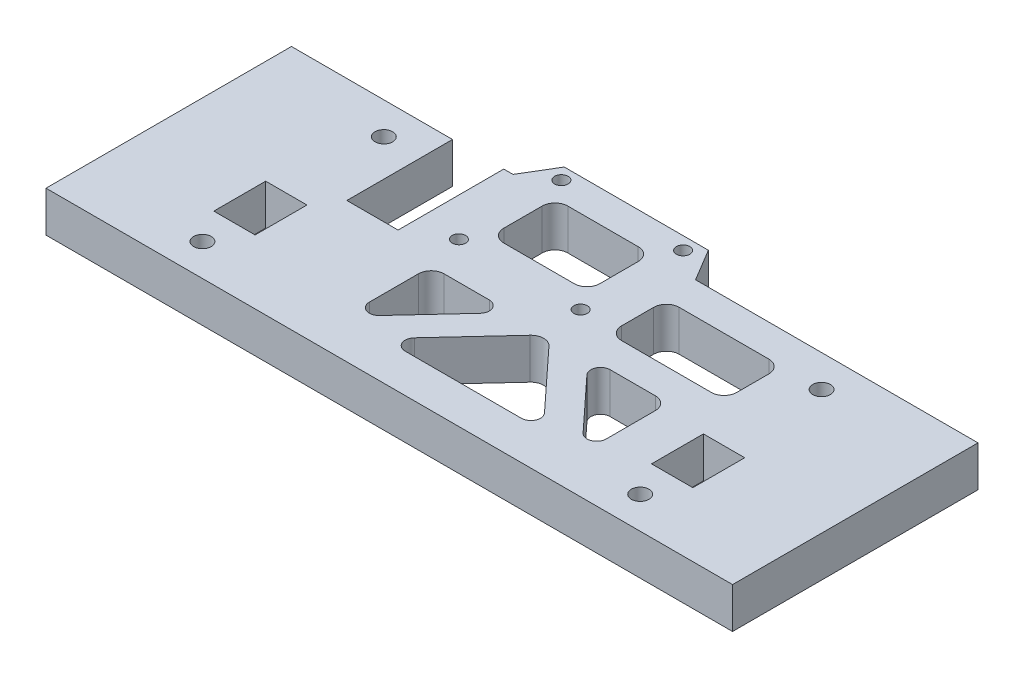
SolidWorks part; units mm, degrees
material "6061 Alloy"
ref_plane "Front Plane" through (0, 0, 0) normal (0, 0, 1) x (1, 0, 0)
ref_plane "Top Plane" through (0, 0, 0) normal (0, 1, 0) x (1, 0, 0)
ref_plane "Right Plane" through (0, 0, 0) normal (1, 0, 0) x (0, 0, -1)
sketch "Sketch1" plane through (0, 0, 0) normal (0, 1, 0) x (1, 0, 0)
  line L0 (107.2, 76.65) -> (107.2, 0) construction
  line L1 (0, 0) -> (214.4, 0)
  line L2 (0, 0) -> (0, 76.65)
  line L4 (214.4, 0) -> (214.4, 76.65)
  line L5 (32.4, 36.2) -> (45.3, 36.2)
  line L6 (32.4, 36.2) -> (32.4, 20)
  line L7 (32.4, 20) -> (45.3, 20)
  line L8 (45.3, 36.2) -> (45.3, 20)
  line L9 (182, 20) -> (169.1, 20)
  line L10 (169.1, 36.2) -> (169.1, 20)
  line L11 (182, 36.2) -> (169.1, 36.2)
  line L12 (182, 36.2) -> (182, 20)
  line L13 (0, 76.65) -> (69.2, 76.65)
  line L14 (69.2, 76.65) -> (75.2, 86.65)
  line L15 (75.2, 86.65) -> (120.2, 86.65)
  line L16 (120.2, 86.65) -> (126.2, 76.65)
  line L17 (126.2, 76.65) -> (214.4, 76.65)
  line L18 (32.4, 28.1) -> (45.3, 28.1) construction
  circle A0 centre (38.85, 66.65) radius 2.75
  circle A5 centre (38.85, 10) radius 2.75
  circle A6 centre (175.55, 66.65) radius 2.75
  circle A7 centre (175.55, 10) radius 2.75
  dimension "D12" = 5.5
  dimension "D16" = 5.5
  dimension "D1" = 214.4
  dimension "D2" = 76.65
  dimension "D3" = 20
  dimension "D5" = 61.9
  dimension "D6" = 12.9
  dimension "D4" = 10
  dimension "D7" = 6
  dimension "D8" = 38
  dimension "D9" = 76.65
  dimension "D10" = 45
  dimension "D11" = 16.2
  dimension "D14" = 6
  dimension "D13" = 10
  dimension "D15" = 10
extrude "Boss-Extrude1" add sketch "Sketch1" along normal blind 12.7
sketch "Sketch2" plane through (0, 12.7, 0) normal (0, 1, 0) x (1, 0, 0)
  line L1 (50.3, 85.2461) -> (66.3, 85.2461)
  line L2 (50.3, 85.2461) -> (50.3, 43.65)
  line L3 (50.3, 43.65) -> (66.3, 43.65)
  line L4 (66.3, 85.2461) -> (66.3, 43.65)
  line L5 (45.3, 20) -> (45.3, 36.2) construction
  line L12 (69.2, 76.65) -> (0, 76.65) construction
  dimension "D1" = 5
  dimension "D2" = 16
  dimension "D3" = 33
extrude "Cut-Extrude1" cut sketch "Sketch2" against normal through all
sketch "Sketch3" plane through (0, 12.7, 0) normal (0, 1, 0) x (1, 0, 0)
  line L1 (66.3, 43.65) -> (66.3, 76.65) construction
  line L2 (120.2, 86.65) -> (75.2, 86.65) construction
  circle A0 centre (78.3, 82.65) radius 2.1
  circle A1 centre (78.3, 50.65) radius 2.1
  circle A2 centre (116.3, 82.65) radius 2.1
  circle A3 centre (116.3, 50.65) radius 2.1
  point P9 (0, 0)
  dimension "D2" = 4.2
  dimension "D5" = 4.2
  dimension "D8" = 32
  dimension "D1" = 4
  dimension "D3" = 12
  dimension "D4" = 32
  dimension "D7" = 38
  dimension "D6" = 2
extrude "Cut-Extrude2" cut sketch "Sketch3" against normal through all
sketch "Sketch5" plane through (0, 12.7, 0) normal (0, 1, 0) x (1, 0, 0)
  line L2 (86.5013, 17.6174) -> (101.635, 33.9618)
  line L3 (99.4337, 39) -> (85.3, 39)
  line L8 (81.3, 35) -> (81.3, 19.6556)
  line L11 (0, 0) -> (214.4, 0) construction
  line L12 (66.3, 43.65) -> (66.3, 76.65) construction
  line L13 (115.365, 35.8302) -> (97.965, 17.0382)
  line L14 (118.3, 39) -> (118.3, 12) construction
  line L15 (100.1663, 12) -> (136.4337, 12)
  line L16 (121.235, 35.8302) -> (138.635, 17.0382)
  line L17 (137.1663, 39) -> (151.3, 39)
  line L18 (150.0987, 17.6174) -> (134.965, 33.9618)
  line L19 (155.3, 35) -> (155.3, 19.6556)
  line L20 (120.2, 86.65) -> (75.2, 86.65) construction
  line L21 (86.3, 76.65) -> (108.3, 76.65)
  line L22 (82.3, 72.65) -> (82.3, 60.65)
  line L23 (86.3, 56.65) -> (108.3, 56.65)
  line L24 (112.3, 72.65) -> (112.3, 60.65)
  line L25 (214.4, 76.65) -> (126.2, 76.65) construction
  line L26 (131.1, 66.65) -> (159.1, 66.65)
  line L27 (127.1, 62.65) -> (127.1, 52.65)
  line L28 (131.1, 48.65) -> (159.1, 48.65)
  line L29 (163.1, 62.65) -> (163.1, 52.65)
  line L30 (169.1, 36.2) -> (169.1, 20) construction
  arc A0 (121.235, 35.8302) -> (115.365, 35.8302) centre (118.3, 33.1125) ccw
  arc A1 (155.3, 35) -> (151.3, 39) centre (151.3, 35) ccw
  arc A2 (81.3, 35) -> (85.3, 39) centre (85.3, 35) cw
  arc A3 (112.3, 72.65) -> (108.3, 76.65) centre (108.3, 72.65) ccw
  arc A4 (108.3, 56.65) -> (112.3, 60.65) centre (108.3, 60.65) ccw
  arc A5 (82.3, 60.65) -> (86.3, 56.65) centre (86.3, 60.65) ccw
  arc A6 (82.3, 72.65) -> (86.3, 76.65) centre (86.3, 72.65) cw
  arc A7 (150.0987, 17.6174) -> (155.3, 19.6556) centre (152.3, 19.6556) ccw
  arc A8 (134.965, 33.9618) -> (137.1663, 39) centre (137.1663, 36) cw
  arc A9 (86.5013, 17.6174) -> (81.3, 19.6556) centre (84.3, 19.6556) cw
  arc A10 (136.4337, 12) -> (138.635, 17.0382) centre (136.4337, 15) ccw
  arc A11 (100.1663, 12) -> (97.965, 17.0382) centre (100.1663, 15) cw
  arc A12 (101.635, 33.9618) -> (99.4337, 39) centre (99.4337, 36) ccw
  arc A13 (163.1, 62.65) -> (159.1, 66.65) centre (159.1, 62.65) ccw
  arc A14 (159.1, 48.65) -> (163.1, 52.65) centre (159.1, 52.65) ccw
  arc A15 (127.1, 52.65) -> (131.1, 48.65) centre (131.1, 52.65) ccw
  arc A16 (127.1, 62.65) -> (131.1, 66.65) centre (131.1, 62.65) cw
  point P25 (155.3, 39)
  point P28 (81.3, 39)
  point P33 (112.3, 56.65)
  point P36 (82.3, 56.65)
  point P39 (82.3, 76.65)
  point P42 (155.3, 12)
  point P45 (130.3, 39)
  point P48 (81.3, 12)
  point P51 (143.3, 12)
  point P54 (93.3, 12)
  point P57 (106.3, 39)
  point P68 (163.1, 66.65)
  point P71 (163.1, 48.65)
  point P76 (127.1, 66.65)
  dimension "D11" = 4
  dimension "D12" = 3
  dimension "D13" = 3
  dimension "D14" = 3
  dimension "D19" = 4
  dimension "D1" = 12
  dimension "D2" = 27
  dimension "D3" = 12
  dimension "D4" = 15
  dimension "D5" = 25
  dimension "D6" = 25
  dimension "D7" = 10
  dimension "D8" = 16
  dimension "D9" = 20
  dimension "D10" = 30
  dimension "D15" = 10
  dimension "D16" = 18
  dimension "D17" = 6
  dimension "D18" = 36
extrude "Cut-Extrude3" cut sketch "Sketch5" against normal through all
equation "\"DriveMotorLength\"= 90mm"
equation "\"DriveMotorGap\"= 10mm"
equation "\"AluminumThickness\"= 0.5in"
equation "\"ChassisWidth\"= ( \"DriveMotorLength\" + \"AluminumThickness\" ) * 2 + \"DriveMotorGap\""
equation "\"RepeatMagnumHoleWidth\"= 19.05mm"
equation "\"MortiseWidth\"= 16mm"
equation "\"ChassisScrewThruHole\"= 5.5mm"
equation "\"D11@Sketch1\"=\"MortiseSlotWidth\""
equation "\"D12@Sketch1\"=\"ChassisScrewThruHole\""
equation "\"D16@Sketch1\"=\"ChassisScrewThruHole\""
equation "\"MortiseSlotWidth\"= 16.2mm"
